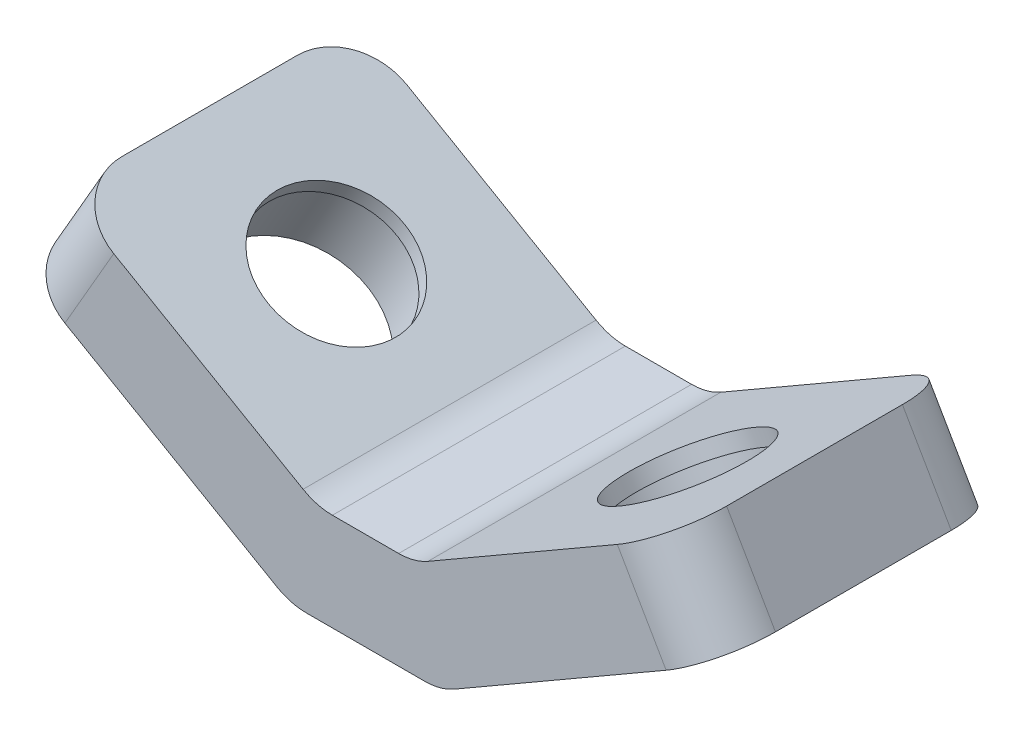
SolidWorks part; units mm, degrees
ref_plane "正面" through (0, 0, 0) normal (0, 0, 1) x (1, 0, 0)
ref_plane "平面" through (0, 0, 0) normal (0, 1, 0) x (1, 0, 0)
ref_plane "右側面" through (0, 0, 0) normal (1, 0, 0) x (0, 0, -1)
sketch "ｽｹｯﾁ1" plane through (0, 0, 0) normal (0, 0, 1) x (1, 0, 0)
  line L0 (0, 0) -> (-14.1506, 8.1699)
  line L1 (-14.1506, 8.1699) -> (-11.6506, 12.5)
  line L2 (-11.6506, 12.5) -> (1.3397, 5)
  line L3 (1.3397, 5) -> (6.3397, 5)
  line L4 (6.3397, 5) -> (19.3301, 12.5)
  line L5 (19.3301, 12.5) -> (21.8301, 8.1699)
  line L6 (21.8301, 8.1699) -> (7.6795, 0)
  line L7 (7.6795, 0) -> (0, 0)
  dimension "D1" = 150
  dimension "D2" = 150
  dimension "D3" = 5
  dimension "D4" = 5
  dimension "D5" = 5
  dimension "D6" = 15
  dimension "D7" = 15
  dimension "D8" = 5
extrude "ﾎﾞｽ - 押し出し1" add sketch "ｽｹｯﾁ1" along normal mid plane 15
sketch "ｽｹｯﾁ2" plane through (0, 0, 0) normal (-0.5, -0.866, 0) x (0, 0, 1)
  line L0 (7.5, 1.3397) -> (7.5, 16.3397) construction
  circle A0 centre (0, 8.8397) radius 4.1
  point P6 (7.5, 8.8397)
  dimension "D1" = 8.2
extrude "ｶｯﾄ - 押し出し1" cut sketch "ｽｹｯﾁ2" against normal through all both and the other way through all
sketch "ｽｹｯﾁ3" plane through (1.9199, -3.3253, 0) normal (0.5, -0.866, 0) x (0, 0, -1)
  line L0 (-7.5, 22.9904) -> (-7.5, 7.9904) construction
  line L1 (-7.5, 22.9904) -> (7.5, 22.9904) construction
  circle A0 centre (0, 15.4904) radius 4.1
  point P4 (-7.5, 15.4904)
  point P7 (0, 22.9904)
  dimension "D1" = 8.2
extrude "ｶｯﾄ - 押し出し2" cut sketch "ｽｹｯﾁ3" against normal through all both and the other way through all
fillet "ﾌｨﾚｯﾄ1" radius 3 8 edges at (20.5801, 10.3349, -7.5) (20.5801, 10.3349, 7.5) (-12.9006, 10.3349, -7.5) (-12.9006, 10.3349, 7.5) (7.6795, 0, 0) (0, 0, 0) (6.3397, 5, 0) (1.3397, 5, 0)
sketch "ｽｹｯﾁ4" plane through (2.5, 4.3301, 0) normal (0.5, 0.866, 0) x (0.866, -0.5, 0)
  circle A0 centre (-8.8397, 0) radius 4.1 construction
  circle A1 centre (-8.8397, 0) radius 4.1
  circle A2 centre (-8.8397, 0) radius 3.5
  dimension "D1" = 7
extrude "ﾎﾞｽ - 押し出し2" add sketch "ｽｹｯﾁ4" against normal blind 0.8
sketch "ｽｹｯﾁ5" plane through (-0.5801, 1.0048, 0) normal (-0.5, 0.866, 0) x (0.866, 0.5, 0)
  circle A0 centre (15.4904, 0) radius 4.1 construction
  circle A1 centre (15.4904, 0) radius 4.1
  circle A2 centre (15.4904, 0) radius 3.5
  dimension "D1" = 7
extrude "ﾎﾞｽ - 押し出し3" add sketch "ｽｹｯﾁ5" against normal blind 0.8
equation "\"D4@ｽｹｯﾁ1\"=\"D3@ｽｹｯﾁ1\""
equation "\"D5@ｽｹｯﾁ1\"=\"D3@ｽｹｯﾁ1\""
equation "\"D2@ｽｹｯﾁ1\"=\"D1@ｽｹｯﾁ1\""
